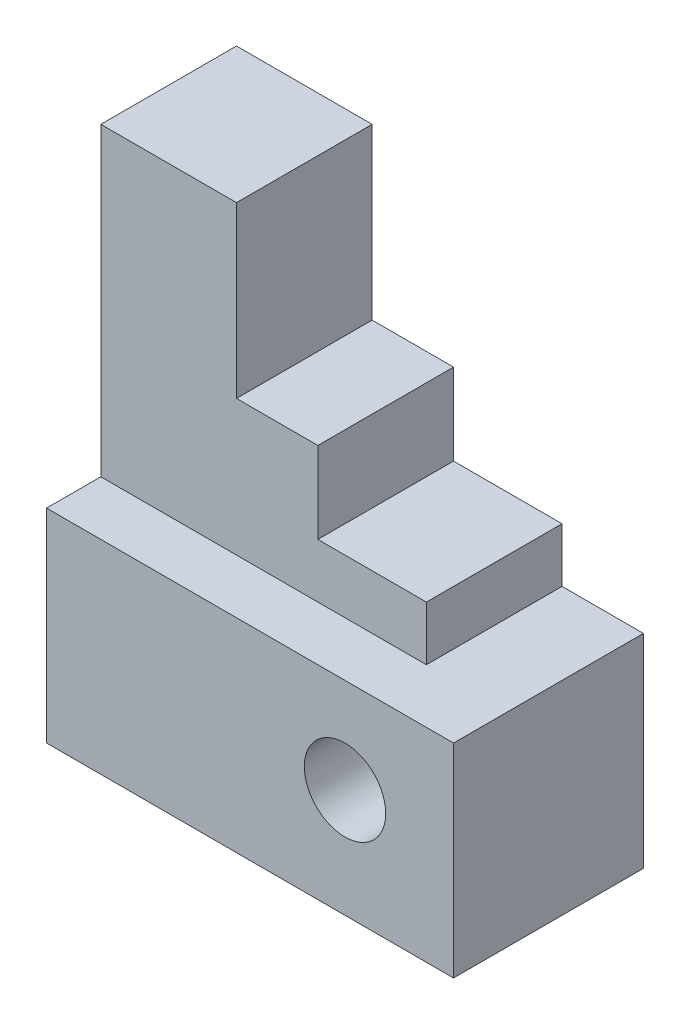
SolidWorks part; units mm, degrees
ref_plane "Front Plane" through (0, 0, 0) normal (0, 0, 1) x (1, 0, 0)
ref_plane "Top Plane" through (0, 0, 0) normal (0, 1, 0) x (1, 0, 0)
ref_plane "Right Plane" through (0, 0, 0) normal (1, 0, 0) x (0, 0, -1)
sketch "Sketch1" plane through (0, 0, 0) normal (0, 1, 0) x (1, 0, 0)
  line L0 (-0.7048, 11.5171) -> (-0.7048, -8.4829)
  line L1 (-20.7048, 11.5171) -> (39.2952, 11.5171)
  line L2 (-20.7048, 11.5171) -> (-20.7048, -16.4829)
  line L3 (-20.7048, -16.4829) -> (39.2952, -16.4829)
  line L4 (39.2952, 11.5171) -> (39.2952, -16.4829)
  line L5 (-20.7048, -8.4829) -> (27.2952, -8.4829)
  line L6 (27.2952, -8.4829) -> (27.2952, 11.5171)
  line L7 (11.2952, -8.4829) -> (11.2952, 11.5171)
  point P11 (0, 0)
  point P12 (0, 0)
  point P13 (0, 0)
  dimension "D1" = 60
  dimension "D2" = 28
  dimension "D3" = 20
  dimension "D4" = 12
  dimension "D5" = 12
extrude "Boss-Extrude1" add sketch "Sketch1" along normal blind 30 from surface contours L6 L5 L2 L3 L4 L1 region at (5.2952, 0, 9.145) starting at plane "Top Plane"
extrude "Boss-Extrude2" add sketch "Sketch1<3>" along normal blind 75 contours L2 L5 L0 L1 region at (-10.7048, 0, -1.5171)
sketch "Sketch1<3>" plane through (0, 0, 0) normal (0, 1, 0) x (1, 0, 0) same geometry as "Sketch1"
extrude "Boss-Extrude3" add sketch "Sketch1<4>" along normal blind 50 contours L5 L7 L1 L0 region at (5.2952, 0, -1.5171)
sketch "Sketch1<4>" plane through (0, 0, 0) normal (0, 1, 0) x (1, 0, 0) same geometry as "Sketch1"
extrude "Boss-Extrude4" add sketch "Sketch1<5>" along normal blind 38 contours L7 L5 L6 L1 region at (19.2952, 0, -1.5171)
sketch "Sketch1<5>" plane through (0, 0, 0) normal (0, 1, 0) x (1, 0, 0) same geometry as "Sketch1"
sketch "Sketch3" plane through (0, 0, 16.4829) normal (0, 0, 1) x (1, 0, 0)
  line L0 (39.2952, 30) -> (39.2952, 0) construction
  circle A0 centre (23.2952, 16) radius 6
  point P4 (0, 0)
  point P6 (57.7127, 4.9105)
  dimension "D1" = 16
  dimension "D2" = 16
extrude "Cut-Extrude1" cut sketch "Sketch3" against normal blind 28
